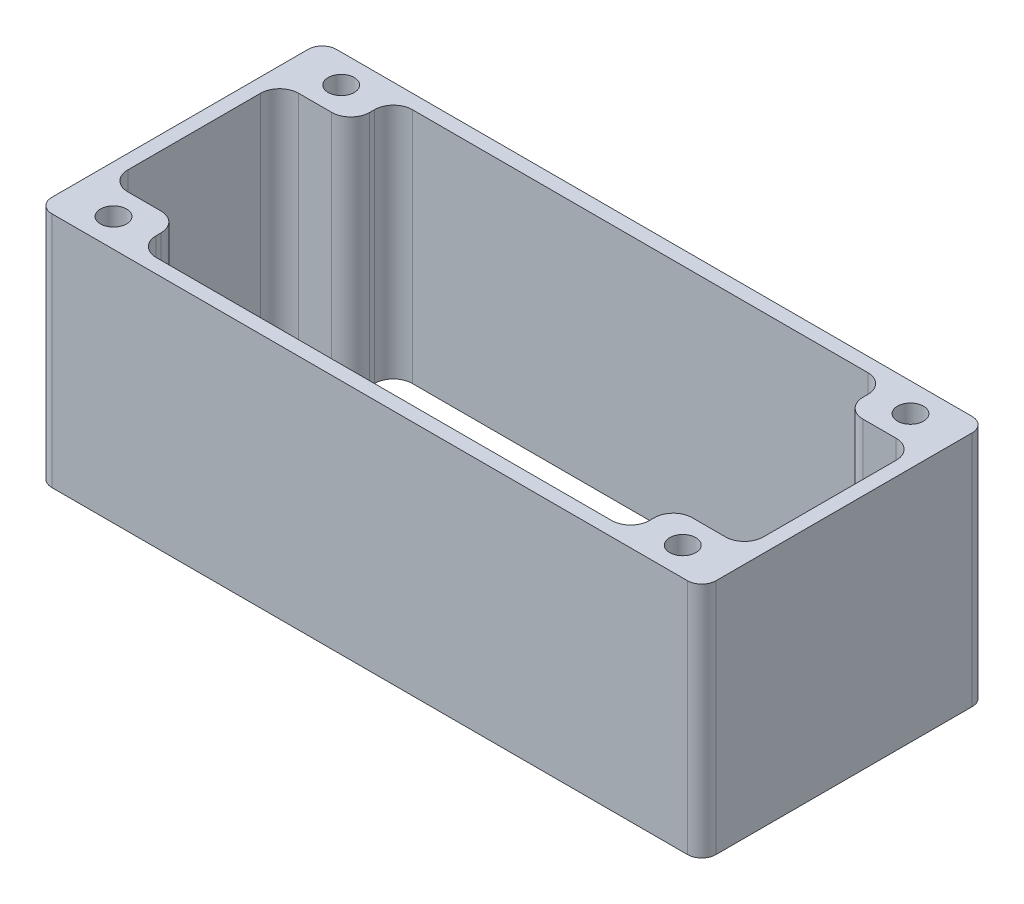
SolidWorks part; units mm, degrees
note: The reader was unsure of these and kept them because the rebuilt part matched: shared geometry of "Sketch1<2>".
ref_plane "Front Plane" through (0, 0, 0) normal (0, 0, 1) x (1, 0, 0)
ref_plane "Top Plane" through (0, 0, 0) normal (0, 1, 0) x (1, 0, 0)
ref_plane "Right Plane" through (0, 0, 0) normal (1, 0, 0) x (0, 0, -1)
sketch "Sketch1" plane through (0, 0, 0) normal (0, 1, 0) x (1, 0, 0)
  line L0 (65, -19) -> (65, 19) construction
  line L1 (-65, -19) -> (65, -19) construction
  line L2 (-65, 19) -> (-65, -19) construction
  line L3 (65, 19) -> (-65, 19) construction
  line L4 (67, 30) -> (-67, 30)
  line L5 (-70, 27) -> (-70, -27)
  line L6 (-67, -30) -> (67, -30)
  line L7 (70, -27) -> (70, 27)
  line L8 (67, 30) -> (-67, 30)
  line L9 (-70, 27) -> (-70, -27)
  line L10 (-67, -30) -> (67, -30)
  line L11 (70, -27) -> (70, 27)
  line L12 (65, -19) -> (65, 19)
  line L13 (-65, -19) -> (65, -19)
  line L14 (-65, 19) -> (-65, -19)
  line L15 (65, 19) -> (-65, 19)
  circle A0 centre (-60, 24) radius 2.75 construction
  circle A1 centre (-60, -24) radius 2.75 construction
  circle A2 centre (60, -24) radius 2.75 construction
  circle A3 centre (60, 24) radius 2.75 construction
  arc A4 (-67, 30) -> (-70, 27) centre (-67, 27) ccw
  arc A5 (-70, -27) -> (-67, -30) centre (-67, -27) ccw
  arc A6 (67, -30) -> (70, -27) centre (67, -27) ccw
  arc A7 (70, 27) -> (67, 30) centre (67, 27) ccw
  arc A8 (-67, 30) -> (-70, 27) centre (-67, 27) ccw
  arc A9 (-70, -27) -> (-67, -30) centre (-67, -27) ccw
  arc A10 (67, -30) -> (70, -27) centre (67, -27) ccw
  arc A11 (70, 27) -> (67, 30) centre (67, 27) ccw
  circle A12 centre (-60, 24) radius 2.75
  circle A13 centre (-60, -24) radius 2.75
  circle A14 centre (60, -24) radius 2.75
  circle A15 centre (60, 24) radius 2.75
  dimension "D1" = 0
extrude "Boss-Extrude1" add sketch "Sketch1" along normal blind 10
extrude "Boss-Extrude2" add sketch "Sketch1<2>" along normal blind 10
sketch "Sketch1<2>" plane through (0, 0, 0) normal (0, 1, 0) x (1, 0, 0) same geometry as "Sketch1"
sketch "Sketch14" plane through (0, 10, 0) normal (0, 1, 0) x (1, 0, 0)
  line L0 (67, 30) -> (-67, 30) construction
  line L1 (52, -27) -> (-52, -27)
  line L2 (52, -27) -> (52, 27)
  line L3 (52, 27) -> (-52, 27)
  line L4 (-52, -27) -> (-52, 27)
  line L5 (52, -27) -> (-52, 27) construction
  line L6 (52, 27) -> (-52, -27) construction
  line L7 (-67, 18) -> (67, 18)
  line L8 (-67, 18) -> (-67, -18)
  line L9 (-67, -18) -> (67, -18)
  line L10 (67, 18) -> (67, -18)
  line L11 (-67, 18) -> (67, -18) construction
  line L12 (-67, -18) -> (67, 18) construction
  line L13 (-70, 27) -> (-70, -27) construction
  line L14 (-67, -30) -> (67, -30) construction
  point P0 (0, 0)
  point P6 (0, 0)
  dimension "D1" = 3
  dimension "D2" = 3
  dimension "D3" = 12
  dimension "D4" = 18
extrude "Cut-Extrude2" cut sketch "Sketch14" against normal through all contours L8 L9 L4 L7 | L4 L9 L2 L7 | L4 L7 L2 L3 | L10 L7 L2 L9 | L9 L4 L1 L2
fillet "Fillet2" radius 4 12 edges at (52, 5, 27) (67, 5, 18) (52, 5, 18) (67, 5, -18) (52, 5, -18) (52, 5, -27) (-52, 5, 27) (-52, 5, 18) (-67, 5, 18) (-67, 5, -18) (-52, 5, -18) (-52, 5, -27)
sketch "Sketch15" plane through (0, 10, 0) normal (0, 1, 0) x (1, 0, 0)
  line L0 (67, 30) -> (-67, 30) construction
  line L1 (70, -27) -> (70, 27) construction
  line L2 (-67, -30) -> (67, -30) construction
  line L3 (-70, 27) -> (-70, -27) construction
  line L4 (67, 30) -> (-67, 30)
  line L5 (70, -27) -> (70, 27)
  line L6 (-67, -30) -> (67, -30)
  line L7 (-70, 27) -> (-70, -27)
  line L12 (56, -18) -> (63, -18)
  line L13 (52, -23) -> (52, -22)
  line L14 (-48, -27) -> (48, -27)
  line L15 (-52, -22) -> (-52, -23)
  line L16 (-63, -18) -> (-56, -18)
  line L17 (-67, 14) -> (-67, -14)
  line L18 (-56, 18) -> (-63, 18)
  line L19 (-52, 23) -> (-52, 22)
  line L20 (48, 27) -> (-48, 27)
  line L21 (52, 22) -> (52, 23)
  line L22 (63, 18) -> (56, 18)
  line L23 (67, -14) -> (67, 14)
  line L24 (56, -18) -> (63, -18)
  line L25 (52, -23) -> (52, -22)
  line L26 (-48, -27) -> (48, -27)
  line L27 (-52, -22) -> (-52, -23)
  line L28 (-63, -18) -> (-56, -18)
  line L29 (-67, 14) -> (-67, -14)
  line L30 (-56, 18) -> (-63, 18)
  line L31 (-52, 23) -> (-52, 22)
  line L32 (48, 27) -> (-48, 27)
  line L33 (52, 22) -> (52, 23)
  line L34 (63, 18) -> (56, 18)
  line L35 (67, -14) -> (67, 14)
  arc A0 (70, 27) -> (67, 30) centre (67, 27) ccw construction
  circle A1 centre (-60, 24) radius 2.75
  circle A2 centre (-60, 24) radius 2.75
  circle A3 centre (-60, -24) radius 2.75
  circle A4 centre (-60, -24) radius 2.75
  circle A5 centre (60, -24) radius 2.75
  circle A6 centre (60, -24) radius 2.75
  circle A7 centre (60, 24) radius 2.75
  circle A8 centre (60, 24) radius 2.75
  arc A9 (67, -30) -> (70, -27) centre (67, -27) ccw construction
  arc A10 (-70, -27) -> (-67, -30) centre (-67, -27) ccw construction
  arc A11 (-67, 30) -> (-70, 27) centre (-67, 27) ccw construction
  arc A12 (70, 27) -> (67, 30) centre (67, 27) ccw
  arc A13 (67, -30) -> (70, -27) centre (67, -27) ccw
  arc A14 (-70, -27) -> (-67, -30) centre (-67, -27) ccw
  arc A15 (-67, 30) -> (-70, 27) centre (-67, 27) ccw
  arc A20 (56, -18) -> (52, -22) centre (56, -22) ccw
  arc A21 (48, -27) -> (52, -23) centre (48, -23) ccw
  arc A22 (-52, -23) -> (-48, -27) centre (-48, -23) ccw
  arc A23 (-52, -22) -> (-56, -18) centre (-56, -22) ccw
  arc A24 (-67, -14) -> (-63, -18) centre (-63, -14) ccw
  arc A25 (-63, 18) -> (-67, 14) centre (-63, 14) ccw
  arc A26 (-56, 18) -> (-52, 22) centre (-56, 22) ccw
  arc A27 (-48, 27) -> (-52, 23) centre (-48, 23) ccw
  arc A28 (52, 23) -> (48, 27) centre (48, 23) ccw
  arc A29 (52, 22) -> (56, 18) centre (56, 22) ccw
  arc A30 (67, 14) -> (63, 18) centre (63, 14) ccw
  arc A31 (63, -18) -> (67, -14) centre (63, -14) ccw
  arc A32 (56, -18) -> (52, -22) centre (56, -22) ccw
  arc A33 (48, -27) -> (52, -23) centre (48, -23) ccw
  arc A34 (-52, -23) -> (-48, -27) centre (-48, -23) ccw
  arc A35 (-52, -22) -> (-56, -18) centre (-56, -22) ccw
  arc A36 (-67, -14) -> (-63, -18) centre (-63, -14) ccw
  arc A37 (-63, 18) -> (-67, 14) centre (-63, 14) ccw
  arc A38 (-56, 18) -> (-52, 22) centre (-56, 22) ccw
  arc A39 (-48, 27) -> (-52, 23) centre (-48, 23) ccw
  arc A40 (52, 23) -> (48, 27) centre (48, 23) ccw
  arc A41 (52, 22) -> (56, 18) centre (56, 22) ccw
  arc A42 (67, 14) -> (63, 18) centre (63, 14) ccw
  arc A43 (63, -18) -> (67, -14) centre (63, -14) ccw
  dimension "D1" = 0
  dimension "D2" = 0
  dimension "D3" = 0
  dimension "D4" = 0
  dimension "D5" = 0
extrude "Boss-Extrude3" add sketch "Sketch15" along normal blind 40
